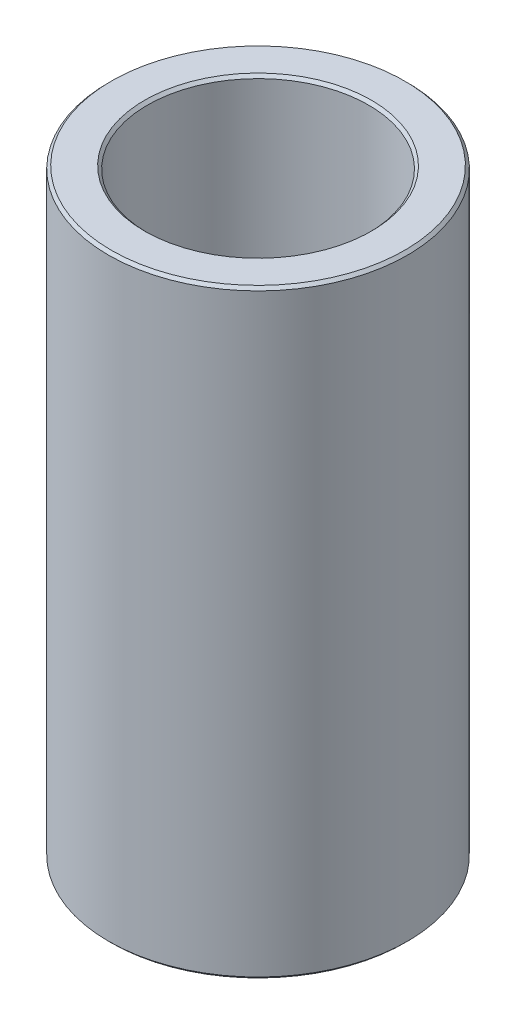
SolidWorks part; units mm, degrees
ref_plane "Front Plane" through (0, 0, 0) normal (0, 0, 1) x (1, 0, 0)
ref_plane "Top Plane" through (0, 0, 0) normal (0, 1, 0) x (1, 0, 0)
ref_plane "Right Plane" through (0, 0, 0) normal (1, 0, 0) x (0, 0, -1)
sketch "Sketch1" plane through (0, 0, 0) normal (0, 1, 0) x (1, 0, 0)
  circle A0 centre (0, 0) radius 47.5
  dimension "SLEEVE_OD" = 95
extrude "Boss-Extrude1" add sketch "Sketch1" along normal blind 190.6388
sketch "Sketch2" plane through (0, 0, 0) normal (0, 1, 0) x (1, 0, 0)
  circle A0 centre (0, 0) radius 35.1612
  dimension "BORE_D" = 70.3224
extrude "Cut-Extrude1" cut sketch "Sketch2" along normal through all
chamfer "Chamfer1" distance 0.895 angle 45 4 edges at (0, 190.6388, 35.1612) (0, 0, 35.1612) (0, 0, 47.5) (0, 190.6388, 47.5)
